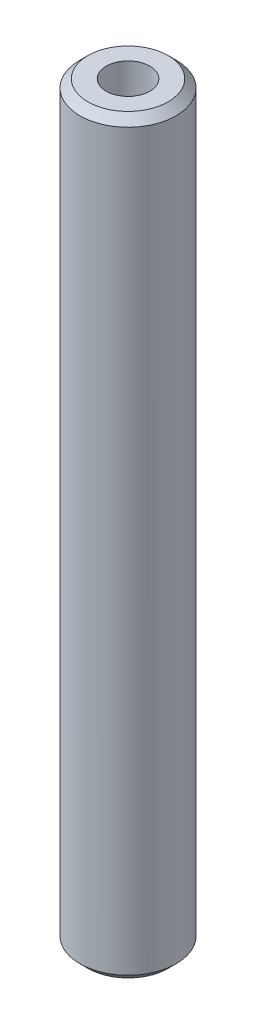
SolidWorks part; units mm, degrees
ref_plane "Front Plane" through (0, 0, 0) normal (0, 0, 1) x (1, 0, 0)
ref_plane "Top Plane" through (0, 0, 0) normal (0, 1, 0) x (1, 0, 0)
ref_plane "Right Plane" through (0, 0, 0) normal (1, 0, 0) x (0, 0, -1)
sketch "Sketch1" plane through (0, 0, 0) normal (0, 1, 0) x (1, 0, 0)
  circle A0 centre (0, 0) radius 27.5
  dimension "SHAFT_OD" = 55
extrude "Boss-Extrude1" add sketch "Sketch1" along normal blind 428.6017
sketch "Sketch2" plane through (0, 0, 0) normal (0, 1, 0) x (1, 0, 0)
  circle A0 centre (0, 0) radius 12.4534
  dimension "BORE_D" = 24.9068
extrude "Cut-Extrude1" cut sketch "Sketch2" along normal through all
chamfer "Chamfer1" distance 4.5927 angle 45 2 edges at (0, 428.6017, 27.5) (0, 0, 27.5)
